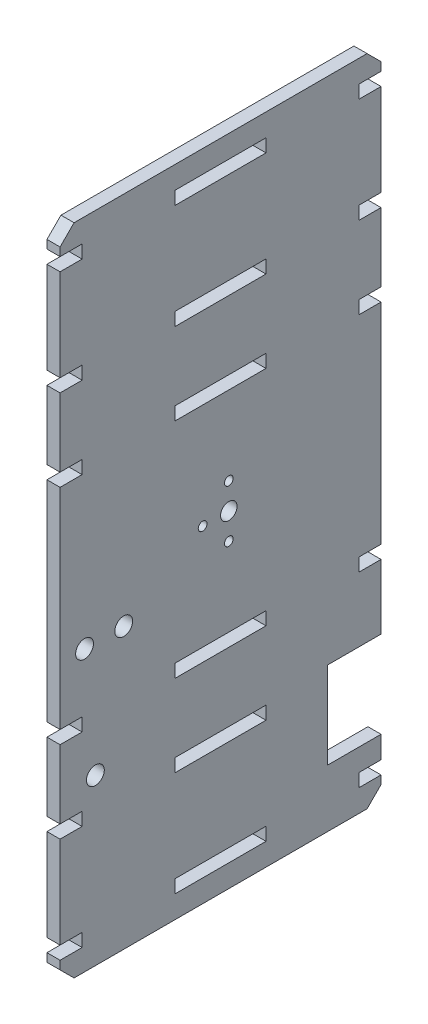
SolidWorks part; units mm, degrees
ref_plane "Front" through (0, 0, 0) normal (0, 0, 1) x (1, 0, 0)
ref_plane "Top" through (0, 0, 0) normal (0, 1, 0) x (1, 0, 0)
ref_plane "Right" through (0, 0, 0) normal (1, 0, 0) x (0, 0, -1)
ref_axis "side-side" through (80.9, 0, 0) along (-1, 0, 0)
ref_axis "up-down" through (0, 50, 0) along (0, -1, 0)
ref_axis "front-back" through (0, 0, -80.9) along (0, 0, 1)
sketch "Sketch1" plane through (0, 0, 0) normal (1, 0, 0) x (0, 0, -1)
  line L1 (-58.293, 118.7905) -> (58.293, 118.7905)
  line L2 (-58.293, 118.7905) -> (-58.293, 110.6625)
  line L3 (-58.293, -118.7905) -> (58.293, -118.7905)
  line L4 (58.293, 118.7905) -> (58.293, 110.6625)
  line L6 (0, 50) -> (0, -50) construction
  line L7 (-58.293, 110.6625) -> (-50.293, 110.6625) construction
  line L8 (58.293, -110.6625) -> (50.293, -110.6625) construction
  line L9 (58.415, -69.422) -> (41.905, -69.422) construction
  line L10 (58.293, -66.374) -> (38.857, -66.374)
  line L11 (58.293, -97.87) -> (58.293, -105.9)
  line L12 (58.293, -97.87) -> (38.857, -97.87)
  line L13 (38.857, -66.374) -> (38.857, -97.87)
  line L14 (55.24, -94.822) -> (41.905, -94.822) construction
  line L16 (0, -110.6625) -> (83.6295, -110.6625) construction
  line L17 (58.293, -105.9) -> (50.293, -105.9)
  line L18 (0, -42.8625) -> (92, -42.8625) construction
  line L19 (58.293, -110.6625) -> (50.293, -110.6625)
  line L20 (50.293, -105.9) -> (50.293, -110.6625)
  line L21 (58.293, -110.6625) -> (58.293, -118.7905)
  line L22 (58.293, -42.8625) -> (58.293, -66.374)
  line L23 (58.293, -38.1) -> (50.293, -38.1)
  line L24 (83.6295, 105.9) -> (0, 105.9) construction
  line L25 (58.293, -42.8625) -> (50.293, -42.8625)
  line L26 (50.293, -38.1) -> (50.293, -42.8625)
  line L27 (83.6295, 67.8) -> (0, 67.8) construction
  line L28 (58.293, 110.6625) -> (50.293, 110.6625)
  line L29 (58.293, 67.8) -> (58.293, 42.8625)
  line L30 (58.293, 105.9) -> (50.293, 105.9)
  line L31 (50.293, 110.6625) -> (50.293, 105.9)
  line L32 (58.293, 38.1) -> (-58.293, 38.1) construction
  line L33 (58.293, 72.5625) -> (50.293, 72.5625)
  line L34 (58.293, 38.1) -> (58.293, -38.1)
  line L35 (58.293, 67.8) -> (50.293, 67.8)
  line L36 (50.293, 72.5625) -> (50.293, 67.8)
  line L37 (0, 67.8) -> (-83.6295, 67.8) construction
  line L38 (58.293, 42.8625) -> (50.293, 42.8625)
  line L39 (-58.293, 105.9) -> (-58.293, 72.5625)
  line L40 (58.293, 38.1) -> (50.293, 38.1)
  line L41 (50.293, 42.8625) -> (50.293, 38.1)
  line L42 (0, 105.9) -> (-83.6295, 105.9) construction
  line L43 (-58.293, 42.8625) -> (-50.293, 42.8625)
  line L44 (-58.293, -42.8625) -> (-58.293, -67.8)
  line L45 (-58.293, 38.1) -> (-50.293, 38.1)
  line L46 (-50.293, 42.8625) -> (-50.293, 38.1)
  line L47 (-58.293, 72.5625) -> (-50.293, 72.5625)
  line L48 (-58.293, 38.1) -> (-58.293, -38.1)
  line L49 (-58.293, 67.8) -> (-50.293, 67.8)
  line L50 (-50.293, 72.5625) -> (-50.293, 67.8)
  line L51 (83.6295, 110.6625) -> (0, 110.6625) construction
  line L52 (-58.293, 110.6625) -> (-50.293, 110.6625)
  line L53 (-58.293, 67.8) -> (-58.293, 42.8625)
  line L54 (-58.293, 105.9) -> (-50.293, 105.9)
  line L55 (-50.293, 110.6625) -> (-50.293, 105.9)
  line L56 (83.6295, 72.5625) -> (0, 72.5625) construction
  line L57 (16.51, 110.6625) -> (-16.51, 110.6625)
  line L58 (16.51, 110.6625) -> (16.51, 105.9)
  line L59 (16.51, 105.9) -> (-16.51, 105.9)
  line L60 (-16.51, 110.6625) -> (-16.51, 105.9)
  line L61 (92, 42.8625) -> (0, 42.8625) construction
  line L62 (16.51, 72.5625) -> (-16.51, 72.5625)
  line L63 (16.51, 72.5625) -> (16.51, 67.8)
  line L64 (16.51, 67.8) -> (-16.51, 67.8)
  line L65 (-16.51, 72.5625) -> (-16.51, 67.8)
  line L67 (16.51, 42.8625) -> (-16.51, 42.8625)
  line L68 (16.51, 42.8625) -> (16.51, 38.1)
  line L69 (16.51, 38.1) -> (-16.51, 38.1)
  line L70 (-16.51, 42.8625) -> (-16.51, 38.1)
  line L72 (-58.293, -38.1) -> (58.293, -38.1) construction
  line L73 (16.51, -38.1) -> (-16.51, -38.1)
  line L74 (16.51, -38.1) -> (16.51, -42.8625)
  line L75 (16.51, -42.8625) -> (-16.51, -42.8625)
  line L77 (-16.51, -38.1) -> (-16.51, -42.8625)
  line L78 (-92, -42.8625) -> (0, -42.8625) construction
  line L79 (0, -67.8) -> (83.6295, -67.8) construction
  line L80 (16.51, -67.8) -> (-16.51, -67.8)
  line L81 (16.51, -67.8) -> (16.51, -72.5625)
  line L82 (16.51, -72.5625) -> (-16.51, -72.5625)
  line L83 (-16.51, -67.8) -> (-16.51, -72.5625)
  line L84 (-83.6295, -72.5625) -> (0, -72.5625) construction
  line L85 (0, -105.9) -> (83.6295, -105.9) construction
  line L86 (16.51, -105.9) -> (-16.51, -105.9)
  line L87 (16.51, -105.9) -> (16.51, -110.6625)
  line L88 (16.51, -110.6625) -> (-16.51, -110.6625)
  line L89 (-16.51, -105.9) -> (-16.51, -110.6625)
  line L90 (-83.6295, -110.6625) -> (0, -110.6625) construction
  line L91 (0, 110.6625) -> (0, 118.7905) construction
  line L92 (58.293, 105.9) -> (58.293, 72.5625)
  line L93 (-58.293, -38.1) -> (-50.293, -38.1)
  line L94 (-58.293, -72.5625) -> (-58.293, -105.9)
  line L95 (-58.293, -42.8625) -> (-50.293, -42.8625)
  line L96 (-50.293, -38.1) -> (-50.293, -42.8625)
  line L97 (-58.293, -67.8) -> (-50.293, -67.8)
  line L98 (-58.293, -110.6625) -> (-58.293, -118.7905)
  line L99 (-58.293, -72.5625) -> (-50.293, -72.5625)
  line L100 (-50.293, -67.8) -> (-50.293, -72.5625)
  line L101 (-58.293, -105.9) -> (-50.293, -105.9)
  line L103 (-58.293, -110.6625) -> (-50.293, -110.6625)
  line L104 (-50.293, -105.9) -> (-50.293, -110.6625)
  circle A0 centre (3, 9.5191) radius 1.5875
  circle A1 centre (-6.5191, 0) radius 1.5875
  circle A2 centre (3, -9.5191) radius 1.5875
  circle A3 centre (3, 0) radius 3
  circle A4 centre (-35.174, -17.15) radius 3.2385
  circle A5 centre (-49.398, -17.15) radius 3.2385
  circle A6 centre (-45.464, -58.873) radius 3.2385
  point P8 (0, 118.7905)
  point P118 (-16.51, 108.2813)
  point P149 (3, 9.5191)
  point P151 (-6.5191, 0)
  point P153 (3, -9.5191)
  point P155 (3, 0)
  point P156 (-35.174, -17.15)
  point P158 (-49.398, -17.15)
  point P160 (-45.464, -58.873)
  dimension "D8" = 6.477
  dimension "D9" = 6
  dimension "D10" = 3.175
  dimension "D1" = 33.02
  dimension "D2" = 8.128
  dimension "D3" = 8.128
  dimension "D4" = 3.048
  dimension "D5" = 3.048
  dimension "D6" = 3.048
  dimension "D7" = 8
extrude "Boss-Extrude1" add sketch "Sketch1" against normal blind 4.7625
chamfer "Chamfer1" distance 5.08 angle 45 4 edges at (-2.3813, 118.7905, 58.293) (-2.3813, 118.7905, -58.293) (-2.3813, -118.7905, 58.293) (-2.3813, -118.7905, -58.293)
